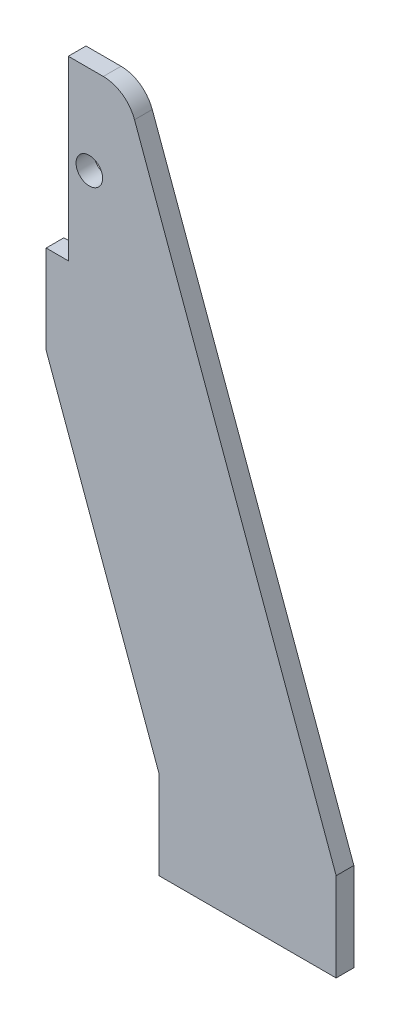
SolidWorks part; units mm, degrees
ref_plane "Alzado" through (0, 0, 0) normal (0, 0, 1) x (1, 0, 0)
ref_plane "Planta" through (0, 0, 0) normal (0, 1, 0) x (1, 0, 0)
ref_plane "Vista lateral" through (0, 0, 0) normal (1, 0, 0) x (0, 0, -1)
sketch "Croquis1" plane through (0, 0, 0) normal (0, 0, 1) x (1, 0, 0)
  line L0 (80, 0) -> (80, 40)
  line L1 (-40.9558, 300) -> (-25.1354, 300)
  line L2 (-50.9558, 220) -> (-50.9558, 180)
  line L3 (0, 0) -> (80, 0)
  line L4 (-11.04, 290.1303) -> (80, 40)
  line L7 (-50.9558, 220) -> (-40.9558, 220)
  line L8 (-40.9558, 300) -> (-40.9558, 220)
  line L9 (-50.9558, 180) -> (0, 40)
  line L11 (0, 40) -> (0, 0)
  arc A2 (-11.04, 290.1303) -> (-25.1354, 300) centre (-25.1354, 285) ccw
  dimension "D7" = 110
  dimension "D9" = 15
  dimension "D1" = 40
  dimension "D2" = 300
  dimension "D3" = 80
  dimension "D4" = 80
  dimension "D5" = 10
  dimension "D6" = 40
  dimension "D8" = 40
  dimension "D10" = 110
extrude "Saliente-Extruir1" add sketch "Croquis1" along normal blind 8
sketch "Croquis2" plane through (0, 0, 0) normal (0, 0, -1) x (-1, 0, 0)
  line L0 (25.1354, 300) -> (40.9558, 300) construction
  line L1 (40.9558, 300) -> (40.9558, 220) construction
  circle A0 centre (31.4558, 260) radius 6
  dimension "D3" = 12
  dimension "D1" = 40
  dimension "D2" = 9.5
extrude "Cortar-Extruir1" cut sketch "Croquis2" against normal through all
hole_wizard "Perforador para roscar para macho de roscar para M43" positions "Croquis3" profile "Croquis4" hole size "M4" standard "DIN"
sketch "Croquis3" plane through (-40.9558, 0, 0) normal (-1, 0, 0) x (0, 0, 1)
  line L0 (5, 220) -> (5, 300)
  line L1 (8, 220) -> (0, 220) construction
  line L2 (8, 300) -> (0, 300) construction
  line L4 (0, 288) -> (8, 288)
  line L5 (0, 300) -> (0, 220) construction
  line L6 (8, 300) -> (8, 220) construction
  line L8 (0, 232) -> (8, 232)
  point P21 (5, 288)
  point P23 (5, 232)
  point P26 (4, 288)
  point P27 (0, 0)
  point P28 (5, 232)
  point P29 (5, 288)
  dimension "D1" = 12
  dimension "D2" = 12
  dimension "D3" = 3
sketch "Croquis4" plane through (-40.9558, 232, 5) normal (0, 1, 0) x (0, 0, 1)
  line L0 (0, 0) -> (0, 10.9914)
  line L1 (0, 10.9914) -> (1.65, 10)
  line L2 (1.65, 10) -> (1.65, 0)
  line L5 (1.65, 0) -> (0, 0)
  line L10 (0, 10.9914) -> (-1.65, 10) construction
  line L11 (0, -6.35) -> (0, 107.95) construction
  dimension "Diámetro de taladro" = 3.3
  dimension "Profundidad de taladro" = 10
  dimension "Ángulo de perforador" = 118
hole_wizard "Taladros de espiga de Ø4.0mm3" positions "Croquis5" profile "Croquis6" hole size "Ø4.0" standard "DIN"
sketch "Croquis5" plane through (-40.9558, 0, 0) normal (-1, 0, 0) x (0, 0, 1)
  line L0 (4, 300) -> (4, 220)
  line L1 (8, 300) -> (0, 300) construction
  line L2 (8, 220) -> (0, 220) construction
  line L4 (8, 300) -> (8, 220) construction
  line L5 (8, 246) -> (0, 246)
  line L6 (0, 300) -> (0, 220) construction
  line L8 (8, 274) -> (0, 274)
  point P21 (4, 274)
  point P24 (4, 274)
  point P27 (0, 0)
  point P28 (4, 246)
  point P29 (5, 277)
  point P30 (4.6646, 274.6187)
  point P31 (4.1632, 268.621)
  point P32 (5, 243)
  point P33 (4, 300)
  dimension "D2" = 26
  dimension "D3" = 26
sketch "Croquis6" plane through (-40.9558, 246, 4) normal (0, 1, 0) x (0, 0, 1)
  line L0 (0, 0) -> (0, 11.2017)
  line L1 (0, 11.2017) -> (2, 10)
  line L2 (2, 10) -> (2, 0)
  line L5 (2, 0) -> (0, 0)
  line L10 (0, 11.2017) -> (-2, 10) construction
  line L11 (0, -6.35) -> (0, 107.95) construction
  dimension "Diámetro de taladro" = 4
  dimension "Profundidad de taladro" = 10
  dimension "Ángulo de perforador" = 118
hole_wizard "Perforador para roscar para macho de roscar para M44" positions "Croquis7" profile "Croquis8" hole size "M4" standard "DIN"
sketch "Croquis7" plane through (0, 0, 0) normal (0, 0, -1) x (-1, 0, 0)
  line L0 (31.4558, 278.25) -> (31.4558, 241.75)
  circle A0 centre (31.4558, 260) radius 6 construction
  point P10 (31.4558, 278.25)
  point P12 (31.4558, 241.75)
  point P17 (31.4558, 241.78)
  point P18 (31.4558, 278.22)
  dimension "D1" = 18.25
  dimension "D2" = 18.25
sketch "Croquis8" plane through (-31.4558, 241.75, 0) normal (1, 0, 0) x (0, 1, 0)
  line L0 (0, 0) -> (0, 7.9914)
  line L1 (0, 7.9914) -> (1.65, 7)
  line L2 (1.65, 7) -> (1.65, 0)
  line L5 (1.65, 0) -> (0, 0)
  line L10 (0, 7.9914) -> (-1.65, 7) construction
  line L11 (0, -6.35) -> (0, 107.95) construction
  dimension "Diámetro de taladro" = 3.3
  dimension "Profundidad de taladro" = 7
  dimension "Ángulo de perforador" = 118
